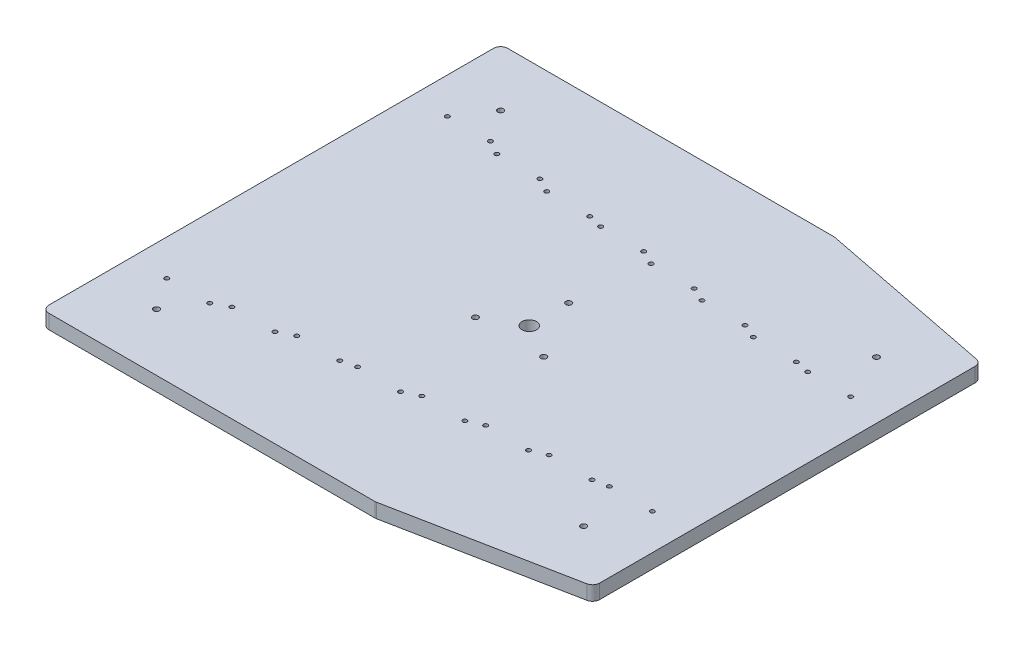
SolidWorks part; units mm, degrees
material "AISI Type 316L stainless steel"
ref_plane "Front Plane" through (0, 0, 0) normal (0, 0, 1) x (1, 0, 0)
ref_plane "Top Plane" through (0, 0, 0) normal (0, 1, 0) x (1, 0, 0)
ref_plane "Right Plane" through (0, 0, 0) normal (1, 0, 0) x (0, 0, -1)
sketch "Sketch1" plane through (0, 0, 0) normal (0, 1, 0) x (1, 0, 0)
  line L1 (-228.6, -203.2) -> (228.6, -203.2)
  line L2 (-228.6, -203.2) -> (-228.6, 203.2)
  line L3 (-228.6, 203.2) -> (228.6, 203.2)
  line L4 (228.6, -203.2) -> (228.6, 203.2)
  line L5 (-228.6, -203.2) -> (228.6, 203.2) construction
  line L6 (-228.6, 203.2) -> (228.6, -203.2) construction
  point P0 (0, 0)
  dimension "D1" = 457.2
  dimension "D2" = 406.4
extrude "Boss-Extrude1" add sketch "Sketch1" along normal blind 12.7
hole_wizard "#6 Clearance Hole1" positions "Sketch2" profile "Sketch3" hole size "#6" standard "ANSI Inch" end condition through all
sketch "Sketch2" plane through (0, 0, 0) normal (0, -1, 0) x (-1, 0, 0)
  line L0 (-228.6, 0) -> (228.6, 0) construction
  line L1 (-228.6, -203.2) -> (-228.6, 203.2) construction
  line L2 (228.6, 203.2) -> (228.6, -203.2) construction
  point P0 (-196.85, 87.8764)
  point P3 (-158.75, 87.8764)
  point P6 (-146.05, 90.4545)
  point P9 (-107.95, 90.4545)
  point P12 (-95.25, 95.8317)
  point P15 (-57.15, 95.8317)
  point P18 (-44.45, 101.5035)
  point P21 (-6.35, 101.5035)
  point P24 (6.35, 107.6173)
  point P27 (44.45, 107.6173)
  point P30 (57.15, 110.711)
  point P33 (95.25, 110.711)
  point P36 (107.95, 117.3404)
  point P39 (146.05, 117.3404)
  point P42 (158.75, 124.2644)
  point P45 (196.85, 124.2644)
  point P56 (196.85, -124.2644)
  point P57 (158.75, -124.2644)
  point P58 (146.05, -117.3404)
  point P59 (107.95, -117.3404)
  point P60 (95.25, -110.711)
  point P61 (57.15, -110.711)
  point P62 (44.45, -107.6173)
  point P63 (6.35, -107.6173)
  point P64 (-6.35, -101.5035)
  point P65 (-44.45, -101.5035)
  point P66 (-57.15, -95.8317)
  point P67 (-95.25, -95.8317)
  point P68 (-107.95, -90.4545)
  point P69 (-146.05, -90.4545)
  point P70 (-158.75, -87.8764)
  point P71 (-196.85, -87.8764)
sketch "Sketch3" plane through (196.85, 0, -87.8764) normal (1, 0, 0) x (0, 0, -1)
  line L0 (0, 0) -> (0, 12.7)
  line L1 (0, 12.7) -> (1.8986, 12.7)
  line L2 (1.8986, 12.7) -> (1.8986, 0)
  line L5 (1.8986, 0) -> (0, 0)
  line L11 (0, -6.35) -> (0, 107.95) construction
  dimension "Thru Hole Dia." = 3.7973
  dimension "Thru Hole Depth" = 12.7
sketch "Sketch4" plane through (0, 12.7, 0) normal (0, 1, 0) x (1, 0, 0)
  line L0 (-196.85, 124.2644) -> (-158.75, 124.2644) construction
  line L1 (-196.85, 130.6144) -> (-158.75, 130.6144)
  line L2 (-196.85, 117.9144) -> (-158.75, 117.9144)
  line L3 (-146.05, 117.3404) -> (-107.95, 117.3404) construction
  line L4 (-146.05, 123.6904) -> (-107.95, 123.6904)
  line L5 (-146.05, 110.9904) -> (-107.95, 110.9904)
  line L6 (-95.25, 110.711) -> (-57.15, 110.711) construction
  line L7 (-95.25, 117.061) -> (-57.15, 117.061)
  line L8 (-95.25, 104.361) -> (-57.15, 104.361)
  line L9 (-44.45, 107.6173) -> (-6.35, 107.6173) construction
  line L10 (-44.45, 113.9673) -> (-6.35, 113.9673)
  line L11 (-44.45, 101.2673) -> (-6.35, 101.2673)
  line L12 (6.35, 101.5035) -> (44.45, 101.5035) construction
  line L13 (6.35, 107.8535) -> (44.45, 107.8535)
  line L14 (6.35, 95.1535) -> (44.45, 95.1535)
  line L15 (57.15, 95.8317) -> (95.25, 95.8317) construction
  line L16 (57.15, 127.8357) -> (95.25, 127.8357)
  line L17 (57.15, 63.8277) -> (95.25, 63.8277)
  line L18 (107.95, 90.4545) -> (146.05, 90.4545) construction
  line L19 (107.95, 96.8045) -> (146.05, 96.8045)
  line L20 (107.95, 84.1045) -> (146.05, 84.1045)
  line L21 (158.75, 87.8764) -> (196.85, 87.8764) construction
  line L22 (158.75, 94.2264) -> (196.85, 94.2264)
  line L23 (158.75, 81.5264) -> (196.85, 81.5264)
  line L24 (-228.6, 0) -> (228.6, 0) construction
  line L25 (-228.6, 203.2) -> (-228.6, -203.2) construction
  line L26 (228.6, -203.2) -> (228.6, 203.2) construction
  line L27 (-196.85, -124.2644) -> (-158.75, -124.2644) construction
  line L28 (-196.85, -130.6144) -> (-158.75, -130.6144)
  line L29 (-196.85, -117.9144) -> (-158.75, -117.9144)
  line L30 (-146.05, -117.3404) -> (-107.95, -117.3404) construction
  line L31 (-146.05, -123.6904) -> (-107.95, -123.6904)
  line L32 (-146.05, -110.9904) -> (-107.95, -110.9904)
  line L33 (-95.25, -110.711) -> (-57.15, -110.711) construction
  line L34 (-95.25, -117.061) -> (-57.15, -117.061)
  line L35 (-95.25, -104.361) -> (-57.15, -104.361)
  line L36 (-44.45, -107.6173) -> (-6.35, -107.6173) construction
  line L37 (-44.45, -113.9673) -> (-6.35, -113.9673)
  line L38 (-44.45, -101.2673) -> (-6.35, -101.2673)
  line L39 (6.35, -101.5035) -> (44.45, -101.5035) construction
  line L40 (6.35, -107.8535) -> (44.45, -107.8535)
  line L41 (6.35, -95.1535) -> (44.45, -95.1535)
  line L42 (57.15, -95.8317) -> (95.25, -95.8317) construction
  line L43 (57.15, -127.8357) -> (95.25, -127.8357)
  line L44 (57.15, -63.8277) -> (95.25, -63.8277)
  line L45 (107.95, -90.4545) -> (146.05, -90.4545) construction
  line L46 (107.95, -96.8045) -> (146.05, -96.8045)
  line L47 (107.95, -84.1045) -> (146.05, -84.1045)
  line L48 (158.75, -87.8764) -> (196.85, -87.8764) construction
  line L49 (158.75, -94.2264) -> (196.85, -94.2264)
  line L50 (158.75, -81.5264) -> (196.85, -81.5264)
  arc A0 (-196.85, 130.6144) -> (-196.85, 117.9144) centre (-196.85, 124.2644) ccw
  arc A1 (-158.75, 117.9144) -> (-158.75, 130.6144) centre (-158.75, 124.2644) ccw
  arc A2 (-146.05, 123.6904) -> (-146.05, 110.9904) centre (-146.05, 117.3404) ccw
  arc A3 (-107.95, 110.9904) -> (-107.95, 123.6904) centre (-107.95, 117.3404) ccw
  arc A6 (-95.25, 117.061) -> (-95.25, 104.361) centre (-95.25, 110.711) ccw
  arc A7 (-57.15, 104.361) -> (-57.15, 117.061) centre (-57.15, 110.711) ccw
  arc A8 (-44.45, 113.9673) -> (-44.45, 101.2673) centre (-44.45, 107.6173) ccw
  arc A9 (-6.35, 101.2673) -> (-6.35, 113.9673) centre (-6.35, 107.6173) ccw
  arc A10 (6.35, 107.8535) -> (6.35, 95.1535) centre (6.35, 101.5035) ccw
  arc A11 (44.45, 95.1535) -> (44.45, 107.8535) centre (44.45, 101.5035) ccw
  arc A12 (57.15, 127.8357) -> (57.15, 63.8277) centre (57.15, 95.8317) ccw
  arc A13 (95.25, 63.8277) -> (95.25, 127.8357) centre (95.25, 95.8317) ccw
  arc A14 (107.95, 96.8045) -> (107.95, 84.1045) centre (107.95, 90.4545) ccw
  arc A15 (146.05, 84.1045) -> (146.05, 96.8045) centre (146.05, 90.4545) ccw
  arc A16 (158.75, 94.2264) -> (158.75, 81.5264) centre (158.75, 87.8764) ccw
  arc A17 (196.85, 81.5264) -> (196.85, 94.2264) centre (196.85, 87.8764) ccw
  circle A22 centre (196.85, 87.8764) radius 1.8987 construction
  arc A27 (-196.85, -130.6144) -> (-196.85, -117.9144) centre (-196.85, -124.2644) cw
  arc A28 (-158.75, -117.9144) -> (-158.75, -130.6144) centre (-158.75, -124.2644) cw
  arc A29 (-146.05, -123.6904) -> (-146.05, -110.9904) centre (-146.05, -117.3404) cw
  arc A30 (-107.95, -110.9904) -> (-107.95, -123.6904) centre (-107.95, -117.3404) cw
  arc A31 (-95.25, -117.061) -> (-95.25, -104.361) centre (-95.25, -110.711) cw
  arc A32 (-57.15, -104.361) -> (-57.15, -117.061) centre (-57.15, -110.711) cw
  arc A33 (-44.45, -113.9673) -> (-44.45, -101.2673) centre (-44.45, -107.6173) cw
  arc A34 (-6.35, -101.2673) -> (-6.35, -113.9673) centre (-6.35, -107.6173) cw
  arc A35 (6.35, -107.8535) -> (6.35, -95.1535) centre (6.35, -101.5035) cw
  arc A36 (44.45, -95.1535) -> (44.45, -107.8535) centre (44.45, -101.5035) cw
  arc A37 (57.15, -127.8357) -> (57.15, -63.8277) centre (57.15, -95.8317) cw
  arc A38 (95.25, -63.8277) -> (95.25, -127.8357) centre (95.25, -95.8317) cw
  arc A39 (107.95, -96.8045) -> (107.95, -84.1045) centre (107.95, -90.4545) cw
  arc A40 (146.05, -84.1045) -> (146.05, -96.8045) centre (146.05, -90.4545) cw
  arc A41 (158.75, -94.2264) -> (158.75, -81.5264) centre (158.75, -87.8764) cw
  arc A42 (196.85, -81.5264) -> (196.85, -94.2264) centre (196.85, -87.8764) cw
  point P4 (-177.8, 124.2644)
  point P16 (-127, 117.3404)
  point P27 (-76.2, 110.711)
  point P32 (-25.4, 107.6173)
  point P41 (25.4, 101.5035)
  point P50 (76.2, 95.8317)
  point P59 (127, 90.4545)
  point P68 (177.8, 87.8764)
  point P96 (-177.8, -124.2644)
  point P103 (-127, -117.3404)
  point P110 (-76.2, -110.711)
  point P117 (-25.4, -107.6173)
  point P124 (25.4, -101.5035)
  point P131 (76.2, -95.8317)
  point P138 (127, -90.4545)
  point P145 (177.8, -87.8764)
extrude "Cut-Extrude1" [suppressed] cut sketch "Sketch4" against normal blind 3.175
sketch "Sketch5" plane through (0, 0, 0) normal (0, -1, 0) x (1, 0, 0)
  line L0 (-228.6, -203.2) -> (228.6, 203.2) construction
  circle A0 centre (0, 0) radius 6.4135
  dimension "D1" = 12.827
extrude "Cut-Extrude2" cut sketch "Sketch5" against normal through all
sketch "Sketch6" plane through (0, 0, 0) normal (0, -1, 0) x (1, 0, 0)
  line L0 (-228.6, -203.2) -> (-228.6, 203.2) construction
  line L1 (-192.913, -121.9914) -> (-196.85, -119.7184)
  line L2 (-196.85, -119.7184) -> (-200.787, -121.9914)
  line L3 (-200.787, -121.9914) -> (-200.787, -126.5374)
  line L4 (-200.787, -126.5374) -> (-196.85, -128.8105)
  line L5 (-196.85, -128.8105) -> (-192.913, -126.5374)
  line L6 (-192.913, -126.5374) -> (-192.913, -121.9914)
  circle A0 centre (-196.85, -124.2644) radius 3.937 construction
  dimension "D1" = 7.874
extrude "Cut-Extrude3" cut sketch "Sketch6" against normal blind 3.175
pattern_sketch "Sketch-Pattern1" of "Cut-Extrude3" driven by "Sketch2"
hole_wizard "#10 Clearance Hole1" positions "Sketch7" profile "Sketch9" hole size "#10" standard "ANSI Inch" end condition through all
sketch "Sketch7" plane through (0, 12.7, 0) normal (0, 1, 0) x (1, 0, 0)
  line L0 (0, 0) -> (0, 34.925) construction
  line L5 (0, 0) -> (30.2459, -17.4625) construction
  line L6 (0, 0) -> (-30.2459, -17.4625) construction
  circle A0 centre (0, 0) radius 34.925 construction
  point P8 (0, 34.925)
  point P28 (30.2459, -17.4625)
  point P29 (-30.2459, -17.4625)
  dimension "D1" = 69.85
sketch "Sketch9" plane through (-30.2459, 12.7, 17.4625) normal (1, 0, 0) x (0, 0, 1)
  line L0 (0, 0) -> (0, 12.7)
  line L1 (0, 12.7) -> (2.5527, 12.7)
  line L2 (2.5527, 12.7) -> (2.5527, 0)
  line L5 (2.5527, 0) -> (0, 0)
  line L11 (0, -6.35) -> (0, 107.95) construction
  dimension "Thru Hole Dia." = 5.1054
  dimension "Thru Hole Depth" = 12.7
sketch "Sketch10" plane through (0, 12.7, 0) normal (0, 1, 0) x (1, 0, 0)
  line L0 (67.0352, -203.2) -> (228.6, -171.45)
  line L1 (-228.6, -203.2) -> (228.6, -203.2) construction
  line L2 (228.6, -203.2) -> (228.6, 203.2) construction
  line L3 (228.6, -171.45) -> (228.6, -203.2)
  line L4 (228.6, -203.2) -> (67.0352, -203.2)
  line L5 (228.6, 0) -> (-228.6, 0) construction
  line L6 (-228.6, 203.2) -> (-228.6, -203.2) construction
  line L7 (228.6, 203.2) -> (67.0352, 203.2)
  line L8 (228.6, 171.45) -> (228.6, 203.2)
  line L9 (67.0352, 203.2) -> (228.6, 171.45)
  circle A0 centre (196.85, 87.8764) radius 1.8987 construction
  dimension "D1" = 31.75
extrude "Cut-Extrude4" cut sketch "Sketch10" against normal through all
fillet "Fillet1" radius 6.35 6 edges at (-228.6, 6.35, 203.2) (-228.6, 6.35, -203.2) (228.6, 6.35, -171.45) (228.6, 6.35, 171.45) (67.0352, 6.35, -203.2) (67.0352, 6.35, 203.2)
hole_wizard "#10 Clearance Hole2" positions "Sketch11" profile "Sketch12" hole size "#10" standard "ANSI Inch" end condition through all
sketch "Sketch11" plane through (0, 12.7, 0) normal (0, 1, 0) x (1, 0, 0)
  line L9 (-222.25, -203.2) -> (66.4172, -203.2) construction
  line L11 (-228.6, 196.85) -> (-228.6, -196.85) construction
  line L12 (228.6, -166.2264) -> (228.6, 166.2264) construction
  line L14 (223.4745, -172.4572) -> (67.6417, -203.0808) construction
  line L16 (228.6, 0) -> (-228.6, 0) construction
  point P39 (177.8, -129.6614)
  point P41 (-177.8, -152.4)
  point P67 (-177.8, 152.4)
  point P68 (177.8, 129.6614)
  dimension "D1" = 50.8
  dimension "D2" = 50.8
  dimension "D3" = 50.8
  dimension "D4" = 50.8
sketch "Sketch12" plane through (177.8, 12.7, 129.6614) normal (1, 0, 0) x (0, 0, 1)
  line L0 (0, 0) -> (0, 12.7)
  line L1 (0, 12.7) -> (2.5527, 12.7)
  line L2 (2.5527, 12.7) -> (2.5527, 0)
  line L5 (2.5527, 0) -> (0, 0)
  line L11 (0, -6.35) -> (0, 107.95) construction
  dimension "Thru Hole Dia." = 5.1054
  dimension "Thru Hole Depth" = 12.7
sketch "Sketch18" plane through (0, 0, 0) normal (0, -1, 0) x (1, 0, 0)
  circle A0 centre (-196.85, -124.2644) radius 6.985
  dimension "D1" = 13.97
extrude "Cut-Extrude6" cut sketch "Sketch18" against normal blind 4.7625
pattern_sketch "Sketch-Pattern2" of "Cut-Extrude6" driven by "Sketch2"
